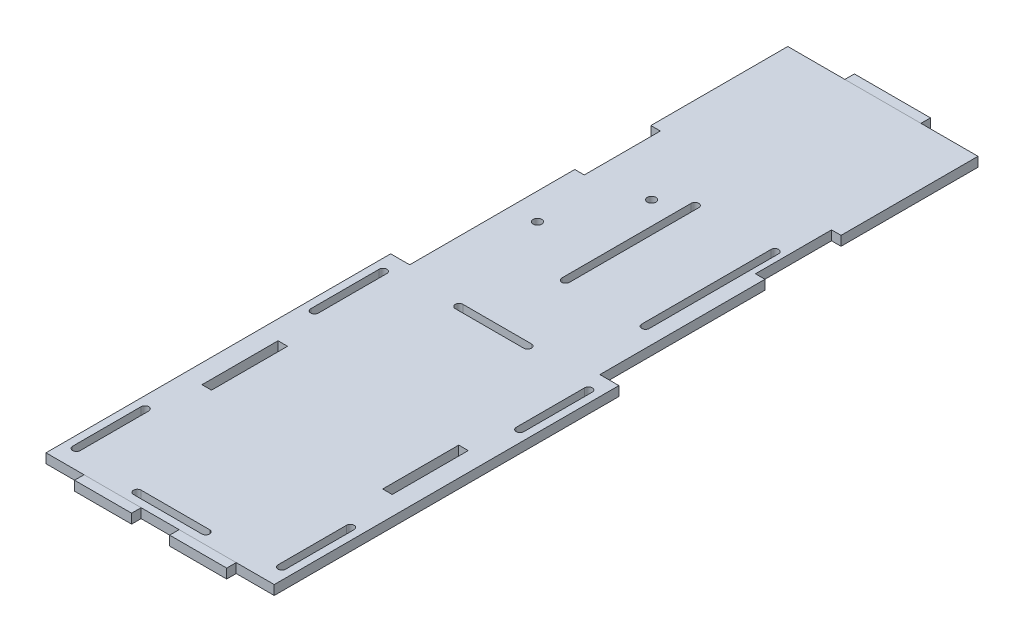
SolidWorks part; units mm, degrees
ref_plane "Front Plane" through (0, 0, 0) normal (0, 0, 1) x (1, 0, 0)
ref_plane "Top Plane" through (0, 0, 0) normal (0, 1, 0) x (1, 0, 0)
ref_plane "Right Plane" through (0, 0, 0) normal (1, 0, 0) x (0, 0, -1)
sketch "Sketch1" plane through (0, 0, 0) normal (0, 1, 0) x (1, 0, 0)
  line L0 (0, 0) -> (38.1, 0) construction
  line L1 (38.1, 0) -> (38.1, 120.65) construction
  line L3 (38.1, 120.65) -> (-38.1, 120.65)
  line L4 (38.1, 120.65) -> (38.1, -120.65)
  line L5 (38.1, -120.65) -> (-38.1, -120.65)
  line L6 (-38.1, 120.65) -> (-38.1, -120.65)
  point P7 (0, 0)
  dimension "D1" = 38.1
  dimension "D2" = 120.65
  dimension "D3" = 76.2
  dimension "D4" = 241.3
extrude "Boss-Extrude1" add sketch "Sketch1" along normal blind 3.175 contours L4 L5 L6 L3
sketch "Sketch5" plane through (0, 3.175, 0) normal (0, 1, 0) x (1, 0, 0)
  line L0 (0, -120.65) -> (0, -5.588) construction
  line L1 (38.1, -120.65) -> (-38.1, -120.65) construction
  line L2 (0, -5.588) -> (-31.75, -5.588) construction
  line L3 (0, -5.588) -> (31.75, -5.588) construction
  line L4 (-31.75, -5.588) -> (-38.1, -5.588)
  line L5 (-38.1, 120.65) -> (-38.1, -120.65) construction
  line L6 (-38.1, -5.588) -> (-31.75, -5.588)
  line L7 (-31.75, -5.588) -> (-31.75, 120.65)
  line L8 (38.1, 120.65) -> (-38.1, 120.65) construction
  line L9 (-31.75, 120.65) -> (-38.1, 120.65)
  line L10 (-38.1, 120.65) -> (-38.1, -5.588)
  line L11 (31.75, -5.588) -> (31.75, 120.65)
  line L12 (31.75, 120.65) -> (38.1, 120.65)
  line L13 (38.1, 120.65) -> (38.1, -5.588)
  line L14 (38.1, 120.65) -> (38.1, -120.65) construction
  line L15 (38.1, -5.588) -> (31.75, -5.588)
  line M10 (38.1, 120.65) -> (-38.1, 120.65)
  line M11 (-38.1, 120.65) -> (-38.1, -120.65)
  line M13 (38.1, -120.65) -> (38.1, 120.65)
  dimension "D1" = 115.062
extrude "Cut-Extrude11" cut sketch "Sketch5" against normal blind 3.175 contours L4 L7 M10 M11 region at (-34.925, 3.175, -57.531)
extrude "Cut-Extrude12" cut sketch "Sketch5<4>" against normal blind 3.175 contours L15 L11 M13 M10 region at (34.925, 3.175, -57.531)
sketch "Sketch5<4>" plane through (0, 3.175, 0) normal (0, 1, 0) x (1, 0, 0) same geometry as "Sketch5"
sketch "Sketch7" plane through (0, 3.175, 0) normal (0, 1, 0) x (1, 0, 0)
  line L0 (-38.1, -120.65) -> (-31.75, -120.65) construction
  line L1 (38.1, -120.65) -> (-38.1, -120.65) construction
  line L2 (-31.75, -120.65) -> (-31.75, -74.93) construction
  line L3 (-31.75, -74.93) -> (-28.575, -74.93) construction
  line L4 (-28.575, -74.93) -> (-28.575, -49.53)
  line L5 (-31.75, -74.93) -> (-31.75, -49.53)
  line L6 (-31.75, -49.53) -> (-28.575, -49.53)
  line L7 (-28.575, -74.93) -> (-31.75, -74.93)
  line L8 (38.1, -120.65) -> (31.75, -120.65) construction
  line L9 (31.75, -120.65) -> (31.75, -74.93) construction
  line L10 (31.75, -74.93) -> (28.575, -74.93)
  line L11 (28.575, -74.93) -> (28.575, -49.53)
  line L12 (28.575, -49.53) -> (31.75, -49.53)
  line L13 (31.75, -49.53) -> (31.75, -74.93)
  line L14 (-31.75, 120.65) -> (-31.75, 74.93) construction
  line L15 (-31.75, -5.588) -> (-31.75, 120.65) construction
  line L16 (-31.75, 74.93) -> (-28.575, 74.93)
  line L17 (-28.575, 74.93) -> (-28.575, 49.53)
  line L18 (-28.575, 49.53) -> (-31.75, 49.53)
  line L19 (-31.75, 49.53) -> (-31.75, 74.93)
  line L20 (31.75, 120.65) -> (31.75, 74.93) construction
  line L21 (31.75, -5.588) -> (31.75, 120.65) construction
  line L22 (31.75, 74.93) -> (28.575, 74.93)
  line L23 (28.575, 74.93) -> (28.575, 49.53)
  line L24 (28.575, 49.53) -> (31.75, 49.53)
  line L25 (31.75, 49.53) -> (31.75, 74.93)
  dimension "D1" = 25.4
extrude "Cut-Extrude13" cut sketch "Sketch7" against normal blind 3.175 contours L7 L5 L6 L4
extrude "Cut-Extrude14" cut sketch "Sketch7<3>" against normal blind 3.175
sketch "Sketch7<3>" plane through (0, 3.175, 0) normal (0, 1, 0) x (1, 0, 0) same geometry as "Sketch7"
sketch "Sketch8" plane through (0, 3.175, 0) normal (0, 1, 0) x (1, 0, 0)
  line L0 (-38.1, -120.65) -> (-25.4, -120.65) construction
  line L1 (38.1, -120.65) -> (-38.1, -120.65) construction
  line L2 (-25.4, -120.65) -> (-25.4, -123.825)
  line L3 (-25.4, -123.825) -> (-6.35, -123.825)
  line L4 (-6.35, -123.825) -> (-6.35, -120.65)
  line L5 (-6.35, -120.65) -> (-25.4, -120.65)
  line L6 (-6.35, -120.65) -> (6.35, -120.65) construction
  line L11 (6.35, -120.65) -> (6.35, -123.825)
  line L12 (6.35, -123.825) -> (25.4, -123.825)
  line L13 (25.4, -123.825) -> (25.4, -120.65)
  line L14 (25.4, -120.65) -> (6.35, -120.65)
  line L15 (0, 120.65) -> (-12.7, 120.65) construction
  line L16 (31.75, 120.65) -> (-31.75, 120.65) construction
  line L17 (-12.7, 120.65) -> (-12.7, 123.825)
  line L18 (-12.7, 123.825) -> (12.7, 123.825)
  line L19 (12.7, 123.825) -> (12.7, 120.65)
  line L20 (12.7, 120.65) -> (-12.7, 120.65)
extrude "Boss-Extrude2" add sketch "Sketch8" against normal blind 3.175 separate body
sketch "Sketch9" plane through (0, 3.175, 0) normal (0, 1, 0) x (1, 0, 0)
  line L0 (0, -120.65) -> (0, -116.84) construction
  line L1 (38.1, -120.65) -> (-38.1, -120.65) construction
  line L2 (-11.43, -116.84) -> (11.43, -116.84) construction
  line L3 (-11.43, -115.57) -> (11.43, -115.57)
  line L4 (-11.43, -118.11) -> (11.43, -118.11)
  line L5 (0, -115.57) -> (0, -9.398) construction
  line L6 (-11.43, -9.398) -> (11.43, -9.398) construction
  line L7 (-11.43, -8.128) -> (11.43, -8.128)
  line L8 (-11.43, -10.668) -> (11.43, -10.668)
  line L9 (38.1, -120.65) -> (34.29, -120.65) construction
  line L10 (34.29, -120.65) -> (34.29, -114.3) construction
  line L11 (34.29, -114.3) -> (34.29, -91.44) construction
  line L14 (-38.1, -120.65) -> (-34.29, -120.65) construction
  line L15 (-34.29, -120.65) -> (-34.29, -114.3) construction
  line L16 (-34.29, -114.3) -> (-34.29, -91.44) construction
  line L19 (-35.56, -114.3) -> (-35.56, -91.44)
  line L20 (-33.02, -114.3) -> (-33.02, -91.44)
  line L21 (33.02, -114.3) -> (33.02, -91.44)
  line L22 (35.56, -114.3) -> (35.56, -91.44)
  line L23 (34.29, -90.17) -> (34.29, -34.798) construction
  line L24 (34.29, -34.798) -> (34.29, -11.938) construction
  line L25 (33.02, -34.798) -> (33.02, -11.938)
  line L26 (35.56, -34.798) -> (35.56, -11.938)
  line L28 (-34.29, -91.44) -> (-34.29, -34.798) construction
  line L29 (-34.29, -34.798) -> (-34.29, -11.938) construction
  line L32 (-35.56, -34.798) -> (-35.56, -11.938)
  line L33 (-33.02, -34.798) -> (-33.02, -11.938)
  arc A0 (-11.43, -115.57) -> (-11.43, -118.11) centre (-11.43, -116.84) ccw
  arc A1 (11.43, -118.11) -> (11.43, -115.57) centre (11.43, -116.84) ccw
  arc A2 (-11.43, -8.128) -> (-11.43, -10.668) centre (-11.43, -9.398) ccw
  arc A3 (11.43, -10.668) -> (11.43, -8.128) centre (11.43, -9.398) ccw
  arc A8 (-35.56, -114.3) -> (-33.02, -114.3) centre (-34.29, -114.3) ccw
  arc A9 (-33.02, -91.44) -> (-35.56, -91.44) centre (-34.29, -91.44) ccw
  arc A10 (33.02, -114.3) -> (35.56, -114.3) centre (34.29, -114.3) ccw
  arc A11 (35.56, -91.44) -> (33.02, -91.44) centre (34.29, -91.44) ccw
  arc A12 (33.02, -34.798) -> (35.56, -34.798) centre (34.29, -34.798) ccw
  arc A13 (35.56, -11.938) -> (33.02, -11.938) centre (34.29, -11.938) ccw
  arc A16 (-35.56, -34.798) -> (-33.02, -34.798) centre (-34.29, -34.798) ccw
  arc A17 (-33.02, -11.938) -> (-35.56, -11.938) centre (-34.29, -11.938) ccw
  point P7 (0, -116.84)
  point P15 (0, -9.398)
  point P26 (34.29, -102.87)
  point P35 (-34.29, -102.87)
  point P43 (34.29, -23.368)
  point P51 (-34.29, -23.368)
extrude "Cut-Extrude15" cut sketch "Sketch9" against normal blind 3.175
sketch "Sketch10" plane through (0, 3.175, 0) normal (0, 1, 0) x (1, 0, 0)
  line L0 (0, -8.128) -> (0, 14.732) construction
  line L1 (11.43, -8.128) -> (-11.43, -8.128) construction
  line L2 (-26.67, 14.732) -> (-26.67, 28.194) construction
  line L3 (-31.75, -5.588) -> (-31.75, 49.53) construction
  line L4 (-31.75, 14.732) -> (-26.67, 14.732) construction
  line L5 (-26.67, 116.332) -> (-16.51, 116.332) construction
  line L6 (-16.51, 116.332) -> (-16.51, 56.896) construction
  line L7 (-16.51, 56.896) -> (-6.35, 56.896) construction
  line L8 (-6.35, 56.896) -> (-6.35, 14.732) construction
  line L9 (-6.35, 14.732) -> (-26.67, 14.732) construction
  line L10 (0, 14.732) -> (-1.27, 14.732) construction
  line L11 (-1.27, 14.732) -> (-1.27, 16.002) construction
  line L12 (-1.27, 16.002) -> (-1.27, 59.182) construction
  line L13 (-2.54, 16.002) -> (-2.54, 59.182)
  line L14 (0, 16.002) -> (0, 59.182)
  line L15 (0, 14.732) -> (25.4, 14.732) construction
  line L16 (25.4, 14.732) -> (25.4, 16.002) construction
  line L17 (25.4, 16.002) -> (25.4, 59.182) construction
  line L18 (24.13, 16.002) -> (24.13, 59.182)
  line L19 (26.67, 16.002) -> (26.67, 59.182)
  line L20 (-26.67, 28.194) -> (-22.86, 28.194) construction
  line L21 (-22.86, 28.194) -> (-22.86, 53.594) construction
  line L22 (-22.86, 53.594) -> (-10.16, 53.594) construction
  arc A0 (-2.54, 16.002) -> (0, 16.002) centre (-1.27, 16.002) ccw
  arc A1 (0, 59.182) -> (-2.54, 59.182) centre (-1.27, 59.182) ccw
  arc A2 (24.13, 16.002) -> (26.67, 16.002) centre (25.4, 16.002) ccw
  arc A3 (26.67, 59.182) -> (24.13, 59.182) centre (25.4, 59.182) ccw
  circle A4 centre (-22.86, 28.194) radius 1.4224
  circle A5 centre (-10.16, 53.594) radius 1.4224
  point P17 (-1.27, 37.592)
  point P23 (25.4, 37.592)
  dimension "D1" = 2.8448
  dimension "D2" = 2.8448
extrude "Cut-Extrude16" cut sketch "Sketch10" against normal blind 3.175
